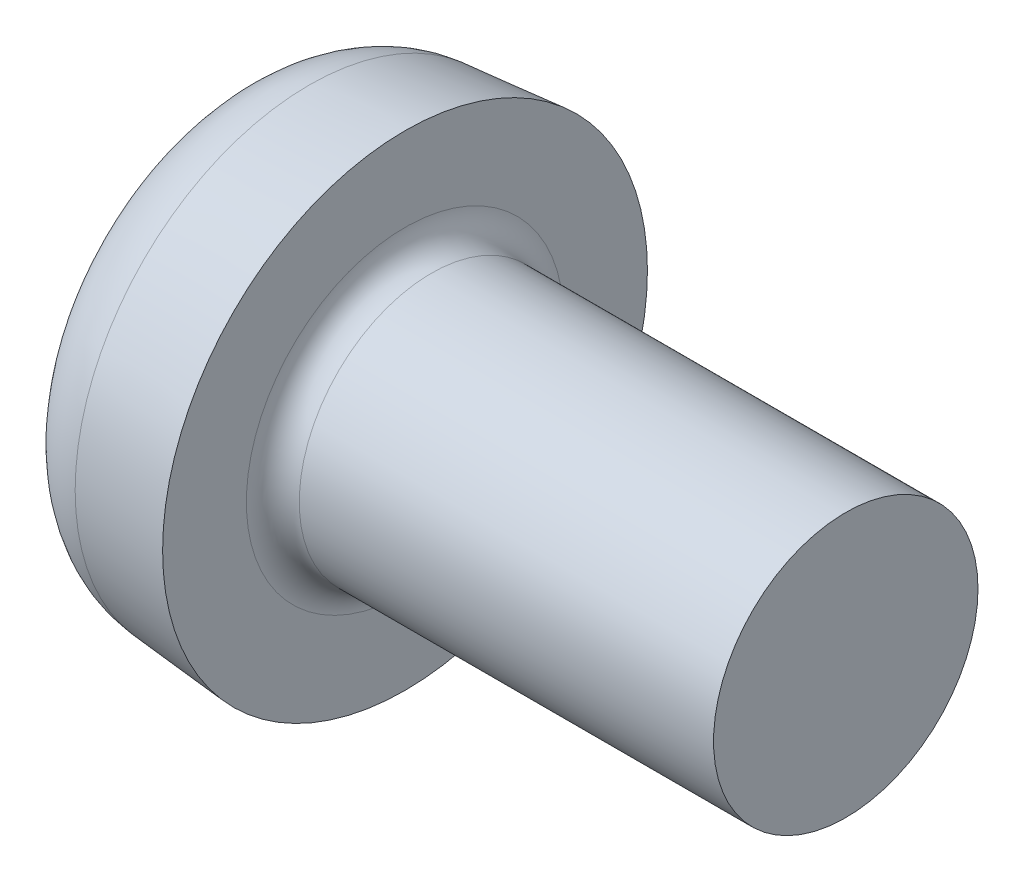
SolidWorks part; units mm, degrees
ref_plane "Front" through (0, 0, 0) normal (0, 0, 1) x (1, 0, 0)
ref_plane "Top" through (0, 0, 0) normal (0, 1, 0) x (1, 0, 0)
ref_plane "Right" through (0, 0, 0) normal (1, 0, 0) x (0, 0, -1)
sketch "Sketch1" plane through (0, 0, 0) normal (0, 0, 1) x (1, 0, 0)
  line L0 (7, 1.5) -> (3, 1.5)
  line L1 (2, 1.8) -> (2, 2.75)
  line L2 (2, 2.75) -> (0, 2.575)
  line L3 (3, 1.5) -> (2.3, 1.5)
  line L4 (7, 1.5) -> (7, 0)
  line L5 (4.5158, 0) -> (-13.5157, 0) construction
  line L6 (7, 0) -> (0, 0)
  line L7 (0, 0) -> (0, 2.575)
  arc A1 (2, 1.8) -> (2.3, 1.5) centre (2.3, 1.8) ccw
  dimension "r" = 0.3
  dimension "D2" = 95
  dimension "dk" = 5.5
  dimension "l" = 5
  dimension "a" = 1
revolve "Base" add sketch "Sketch1" angle 360 about L5
cosmetic thread "ThreadCosmetic1" [suppressed] parameters "bb"=5, "THD_MINOR"=2.459
sketch "Sketch6" plane through (0, 0, 0) normal (1, 0, 0) x (0, 0, -1)
  line L0 (-1.9271, 0) -> (2.0512, 0) construction
  line L1 (0, 1.8651) -> (0, -2.0207) construction
  line L2 (0.35, 0.35) -> (0.35, 1.75)
  line L3 (0.35, 1.75) -> (-0.35, 1.75)
  line L4 (-0.35, 0.35) -> (-0.35, 1.75)
  line L5 (0.35, 0.35) -> (1.75, 0.35)
  line L6 (1.75, 0.35) -> (1.75, -0.35)
  line L7 (-1.75, 0.35) -> (-1.75, -0.35)
  line L8 (-0.35, 0.35) -> (-1.75, 0.35)
  line L9 (-0.35, -0.35) -> (-1.75, -0.35)
  line L10 (0.35, -0.35) -> (1.75, -0.35)
  line L11 (-0.35, -0.35) -> (-0.35, -1.75)
  line L12 (0.35, -1.75) -> (-0.35, -1.75)
  line L13 (0.35, -0.35) -> (0.35, -1.75)
  point P16 (-1.75, 0)
  point P17 (1.75, 0)
extrude "CrossRecess" cut sketch "Sketch6" along normal blind 2
fillet "Fillet5" radius 0.3 4 edges at (1, -0.35, 0.35) (1, -0.35, -0.35) (1, 0.35, 0.35) (1, 0.35, -0.35)
sketch "Sketch8" [suppressed] plane through (0, 0, 0) normal (0, 0, 1) x (1, 0, 0)
  line L0 (12, 4) -> (8.2, 3.5)
  line L1 (8.2, 3.5) -> (5, 3.5)
  line L3 (50, -4) -> (50, 4) construction
  line L4 (5, -6.5) -> (5, 6.5) construction
  line L6 (5, 3.5) -> (5, 14)
  line L7 (5, 14) -> (12, 14)
  line L8 (12, 14) -> (12, 4)
  line L9 (52.4753, 0) -> (42.9594, 0) construction
  dimension "D1" = 23
  dimension "x" = 1.25
fillet "HeadFillet" radius 1 1 edges at (0, 0, -2.575)
draft "Draft1" type of draft neutral plane draft angle 20 faces to draft 4 face at (1.004, -0.0875, 1.75) face at (1.004, -1.75, -0.0875) face at (1.004, 0.0875, -1.75) face at (1.004, 1.75, 0.0875) neutral plane through (0, 0, 0) neutral plane normal (-1, 0, 0) parameters "D1"=20
sketch "Sketch7" plane through (0, 0, 0) normal (1, 0, 0) x (0, 0, -1)
  line L0 (-8.3217, 0) -> (7.4212, 0) construction
  line L1 (0, 7.4989) -> (0, -7.9646) construction
  line L2 (0, 0) -> (6.8599, 6.8599) construction
  line L3 (1.2374, 1.2374) -> (0, 0.6604)
  line L4 (0, 0) -> (-6.8599, 6.8599) construction
  line L5 (1.2374, 1.2374) -> (0.6604, 0)
  line L6 (1.2374, -1.2374) -> (0, -0.6604)
  line L7 (1.2374, -1.2374) -> (0.6604, 0)
  line L8 (-1.2374, -1.2374) -> (0, -0.6604)
  line L9 (-1.2374, -1.2374) -> (-0.6604, 0)
  line L10 (-1.2374, 1.2374) -> (0, 0.6604)
  line L11 (-1.2374, 1.2374) -> (-0.6604, 0)
  dimension "D2" = 20
extrude "Cut-Extrude3" [suppressed] cut sketch "Sketch7" along normal blind 10 draft 20
sketch "Sketch10" plane through (0, 0, 0) normal (0, 0, 1) x (1, 0, 0)
  line L0 (7, 1.2657) -> (7.1353, 1.5)
  line L1 (7.1353, 1.5) -> (7.1353, 1.7705)
  line L2 (7.1353, 1.7705) -> (6.8647, 1.7705)
  line L3 (6.8647, 1.7705) -> (6.8647, 1.5)
  line L4 (6.8647, 1.5) -> (7, 1.2657)
  line L5 (7, 1.5) -> (3, 1.5) construction
  line L6 (7, 1.5) -> (7, 0) construction
  line L7 (0, 0) -> (57.111, 0) construction
  dimension "D1" = 0.2705
revolve "Cut-Revolve10" [suppressed] cut sketch "Sketch10" angle 360 about L7
pattern_linear "LPattern10" [suppressed] count 15 spacing 0.3246 along (-1, 0, 0) of bodies 107
equation "\"D1@Sketch6\" = \"m@Sketch6\" / 5"
equation "\"D1@Sketch8\" = \"d@Sketch8\" + 20"
equation "\"D1@Sketch10\" =  ( \"d@Sketch1\" - \"THD_MINOR@ThreadCosmetic1\" )  / 2"
equation "\"D3@LPattern10\" = \"D1@Sketch10\" * 1.2"
equation "\"D1@LPattern10\" = \"bb@ThreadCosmetic1\" / \"D3@LPattern10\" "
